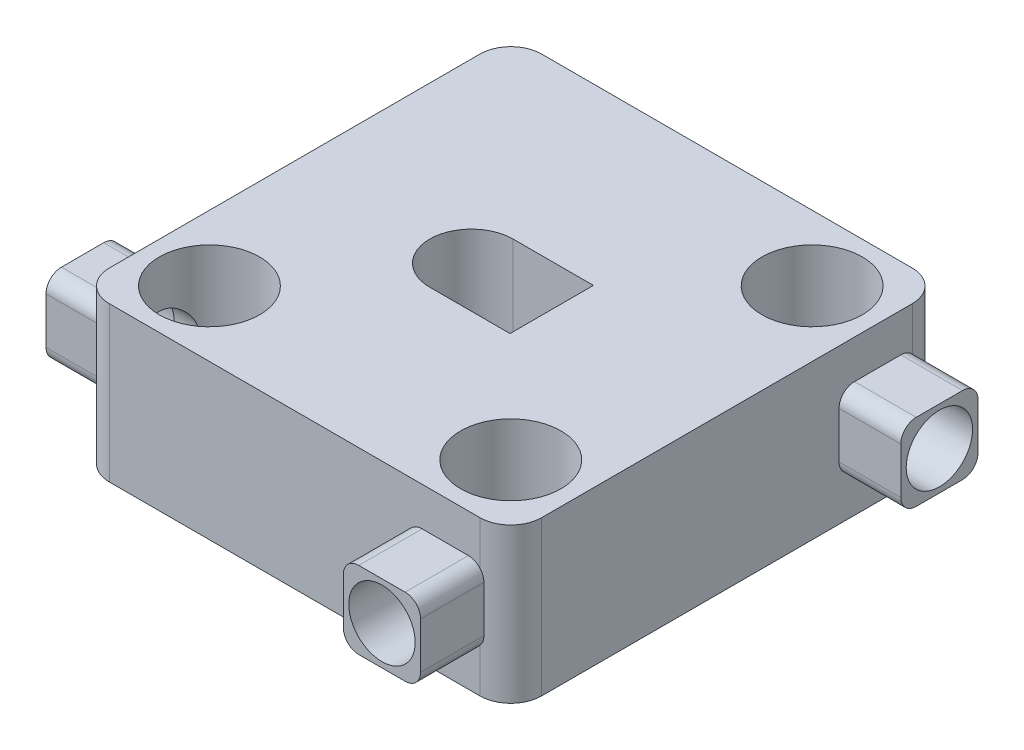
SolidWorks part; units mm, degrees
ref_plane "Front Plane" through (0, 0, 0) normal (0, 0, 1) x (1, 0, 0)
ref_plane "Top Plane" through (0, 0, 0) normal (0, 1, 0) x (1, 0, 0)
ref_plane "Right Plane" through (0, 0, 0) normal (1, 0, 0) x (0, 0, -1)
sketch "Sketch1" plane through (0, 0, 0) normal (0, 1, 0) x (1, 0, 0)
  line L0 (0.9332, 0.6825) -> (28.9332, 0.6825)
  line L1 (0.9332, 0.6825) -> (0.9332, 28.6825)
  line L2 (0.9332, 28.6825) -> (28.9332, 28.6825)
  line L3 (28.9332, 0.6825) -> (28.9332, 28.6825)
  line L4 (17.3832, 17.1825) -> (17.3832, 12.1825) construction
  line L5 (17.3832, 12.1825) -> (12.3832, 12.1825) construction
  line L6 (17.3832, 17.1825) -> (12.3832, 17.1825) construction
  line L7 (0.9332, 0.6825) -> (5.1758, 4.9251) construction
  line L8 (5.1758, 4.9251) -> (24.6905, 24.4399) construction
  line L9 (24.6905, 24.4399) -> (28.9332, 28.6825) construction
  line L10 (24.6905, 24.4399) -> (24.6905, 4.9251) construction
  line L11 (24.6905, 4.9251) -> (5.1758, 4.9251) construction
  line L12 (17.5832, 17.3825) -> (17.5832, 11.9825)
  line L13 (17.5832, 11.9825) -> (12.3832, 11.9825)
  line L14 (17.5832, 17.3825) -> (12.3832, 17.3825)
  line L15 (12.3832, 14.6825) -> (12.3832, 12.1325) construction
  circle A0 centre (5.1758, 4.9251) radius 3.25
  circle A1 centre (24.6905, 4.9251) radius 3.25
  circle A2 centre (24.6905, 24.4399) radius 3.25
  arc A3 (12.3832, 17.1825) -> (12.3832, 12.1825) centre (12.3832, 14.6825) ccw construction
  arc A4 (12.3832, 17.3825) -> (12.3832, 11.9825) centre (12.3832, 14.6825) ccw
  dimension "D2" = 6.5
  dimension "D6" = 5
  dimension "D1" = 28
  dimension "D3" = 6
  dimension "D4" = 2.55
  dimension "D5" = 5
  dimension "D7" = 11.45
  dimension "D8" = 0.2
extrude "Boss-Extrude1" add sketch "Sketch1" along normal blind 10
fillet "Fillet1" radius 2 4 edges at (0.9332, 5, -0.6825) (0.9332, 5, -28.6825) (28.9332, 5, -28.6825) (28.9332, 5, -0.6825)
sketch "Sketch2" plane through (28.9332, 0, 0) normal (1, 0, 0) x (0, 0, -1)
  line L1 (21.9399, 2.5) -> (26.9399, 2.5)
  line L2 (21.9399, 2.5) -> (21.9399, 7.5)
  line L3 (21.9399, 7.5) -> (26.9399, 7.5)
  line L4 (26.9399, 2.5) -> (26.9399, 7.5)
  line L5 (21.9399, 2.5) -> (26.9399, 7.5) construction
  line L6 (21.9399, 7.5) -> (26.9399, 2.5) construction
  line L8 (26.6825, 5) -> (24.4399, 5) construction
  line L9 (26.6825, 0) -> (26.6825, 10) construction
  line L10 (24.4399, 5) -> (24.4399, 0) construction
  line L11 (21.1899, 0) -> (27.6899, 0) construction
  circle A0 centre (24.4399, 5) radius 2.15
  circle A1 centre (24.4399, 5) radius 1.95
  point P0 (24.4399, 5)
  dimension "D1" = 4.3
  dimension "D2" = 3.9
  dimension "D3" = 5
extrude "Boss-Extrude2" add sketch "Sketch2" along normal blind 4 and the other way blind 0.5 contours L3 L4 L1 L2
extrude "Cut-Extrude1" cut sketch "Sketch2<3>" against normal blind 4 and the other way blind 5 contours A1
sketch "Sketch2<3>" plane through (28.9332, 0, 0) normal (1, 0, 0) x (0, 0, -1) same geometry as "Sketch2"
extrude "Cut-Extrude2" cut sketch "Sketch2<4>" against normal blind 0.5 from surface contours A0 starting at face at (32.9332, 5, -22.4899)
sketch "Sketch2<4>" plane through (28.9332, 0, 0) normal (1, 0, 0) x (0, 0, -1) same geometry as "Sketch2"
extrude "Cut-Extrude3" cut sketch "Sketch2<5>" against normal blind 4.1 from surface contours A0 starting at face at (32.9332, 5, -22.2899)
sketch "Sketch2<5>" plane through (28.9332, 0, 0) normal (1, 0, 0) x (0, 0, -1) same geometry as "Sketch2"
sketch "Sketch6" plane through (0.9332, 0, 0) normal (-1, 0, 0) x (0, 0, 1)
  line L0 (-7.4251, 2.5) -> (-2.4251, 2.5)
  line L1 (-7.4251, 2.5) -> (-7.4251, 7.5)
  line L2 (-7.4251, 7.5) -> (-2.4251, 7.5)
  line L3 (-2.4251, 2.5) -> (-2.4251, 7.5)
  line L4 (-7.4251, 2.5) -> (-2.4251, 7.5) construction
  line L5 (-7.4251, 7.5) -> (-2.4251, 2.5) construction
  line L6 (-2.6825, 5) -> (-4.9251, 5) construction
  line L7 (-4.9251, 5) -> (-4.9251, 0) construction
  line L8 (-8.1751, 0) -> (-1.6751, 0) construction
  line L9 (-2.6825, 0) -> (-2.6825, 10) construction
  circle A0 centre (-4.9251, 5) radius 2.15
  circle A1 centre (-4.9251, 5) radius 1.95
  point P0 (-4.9251, 5)
  line M9 (-2.6825, 0) -> (-2.6825, 10)
  dimension "D1" = 3.9
  dimension "D3" = 4.3
  dimension "D2" = 5
sketch "Sketch5" plane through (0, 0, -0.6825) normal (0, 0, -1) x (-1, 0, 0)
  line L0 (-27.1905, 2.5) -> (-22.1905, 2.5)
  line L1 (-27.1905, 2.5) -> (-27.1905, 7.5)
  line L2 (-27.1905, 7.5) -> (-22.1905, 7.5)
  line L3 (-22.1905, 2.5) -> (-22.1905, 7.5)
  line L4 (-27.1905, 2.5) -> (-22.1905, 7.5) construction
  line L5 (-27.1905, 7.5) -> (-22.1905, 2.5) construction
  line L6 (-26.9332, 5) -> (-24.6905, 5) construction
  line L7 (-24.6905, 5) -> (-24.6905, 0) construction
  line L8 (-2.9332, 0) -> (-26.9332, 0) construction
  line L9 (-26.9332, 0) -> (-26.9332, 10) construction
  line L10 (-27.9405, 0) -> (-21.4405, 0) construction
  circle A0 centre (-24.6905, 5) radius 2.15
  circle A1 centre (-24.6905, 5) radius 1.95
  point P0 (-24.6905, 5)
  dimension "D1" = 3.9
  dimension "D3" = 4.3
  dimension "D2" = 5
sketch "Sketch3" plane through (0, 10, 0) normal (0, 1, 0) x (1, 0, 0)
  line L0 (28.3474, 28.0967) -> (1.519, 1.2683) construction
  arc A0 (28.9332, 26.6825) -> (26.9332, 28.6825) centre (26.9332, 26.6825) ccw construction
  arc A1 (0.9332, 2.6825) -> (2.9332, 0.6825) centre (2.9332, 2.6825) ccw construction
  point P0 (28.3474, 28.0967)
  point P1 (1.519, 1.2683)
  point P10 (14.9332, 14.6825)
ref_plane "Plane1" through (0, 0, -14.6825) normal (0, 0, -1) x (-1, 0, 0)
sketch "Sketch4" plane through (0, 0, -14.6825) normal (0, 0, -1) x (-1, 0, 0)
  line L0 (-14.9332, 10) -> (-14.9332, 0) construction
  line L1 (-26.9332, 0) -> (-2.9332, 0) construction
extrude "Boss-Extrude3" add sketch "Sketch6" along normal blind 4.1 contours L2 L1 L0 A0 M9 region at (0.9332, 5, -7.3562)
extrude "Cut-Extrude4" cut sketch "Sketch6<3>" against normal blind 4.1 contours A1
sketch "Sketch6<3>" plane through (0.9332, 0, 0) normal (-1, 0, 0) x (0, 0, 1) same geometry as "Sketch6"
extrude "Boss-Extrude5" add sketch "Sketch5" against normal blind 4.1 contours A1 | A0 A1 | L2 L3 L0 L1 region at (26.7797, 5, -0.6825) region at (24.6905, 5, -0.6825)
extrude "Cut-Extrude5" cut sketch "Sketch5<4>" along normal blind 4.1 contours A1
sketch "Sketch5<4>" plane through (0, 0, -0.6825) normal (0, 0, -1) x (-1, 0, 0) same geometry as "Sketch5"
fillet "Fillet2" radius 1 12 edges at (30.9332, 7.5, -21.9399) (30.9332, 2.5, -21.9399) (30.9249, 2.5, -26.9399) (30.9249, 7.5, -26.9399) (-1.1168, 7.5, -2.6825) (-1.1168, 7.5, -7.4251) (-1.1168, 2.5, -7.4251) (-1.1168, 2.5, -2.6825) (22.1905, 7.5, 1.3675) (22.1905, 2.5, 1.3675) (27.1905, 2.5, 1.3675) (27.1905, 7.5, 1.3675)
